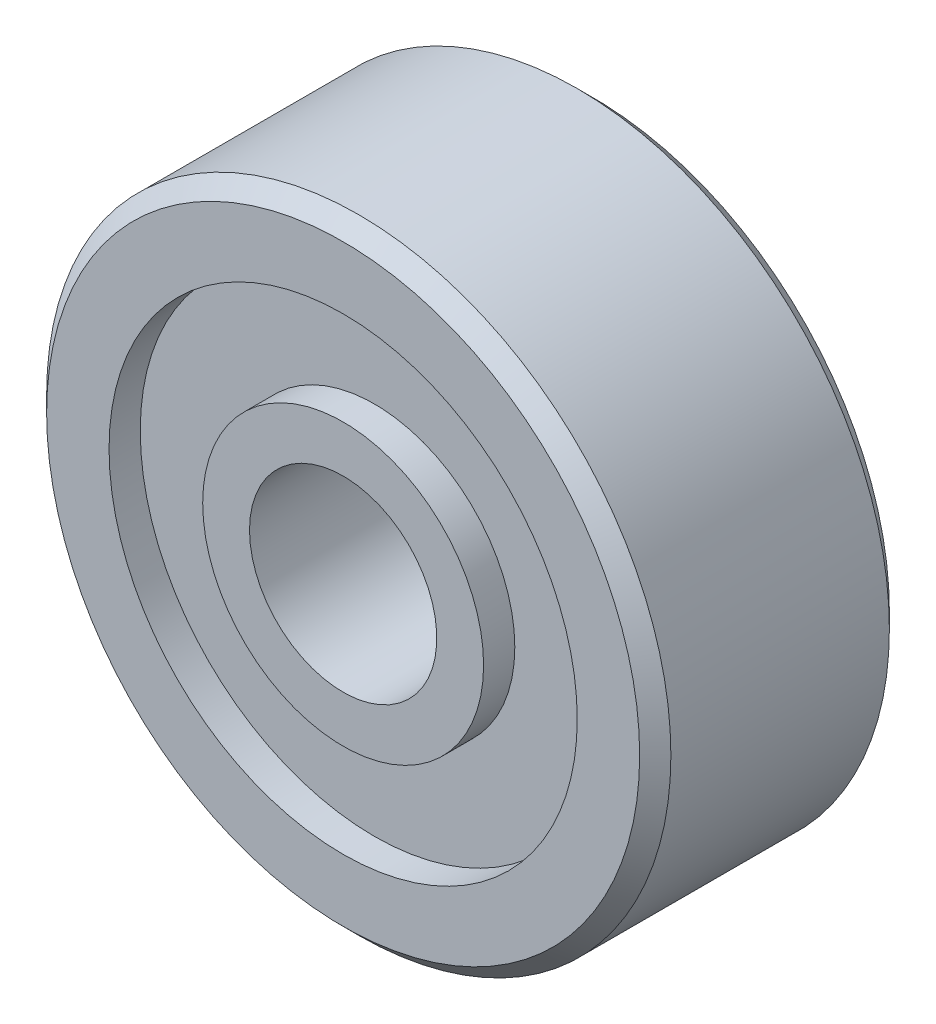
SolidWorks part; units mm, degrees
ref_plane "Front Plane" through (0, 0, 0) normal (0, 0, 1) x (1, 0, 0)
ref_plane "Top Plane" through (0, 0, 0) normal (0, 1, 0) x (1, 0, 0)
ref_plane "Right Plane" through (0, 0, 0) normal (1, 0, 0) x (0, 0, -1)
ref_plane "Plane1" through (0, 0, 0) normal (0, -1, 0) x (1, 0, 0)
sketch "Sketch1" plane through (0, 0, 0) normal (0, -1, 0) x (1, 0, 0)
  line L0 (6.5, 1.25) -> (6.25, 1.5)
  line L1 (6.25, 1.5) -> (5.25, 1.5)
  line L2 (5.25, 1.5) -> (5.25, 1)
  line L3 (5.25, 1) -> (3.75, 1)
  line L4 (3.75, 1) -> (3.75, 1.5)
  line L5 (3.75, 1.5) -> (3, 1.5)
  line L6 (3, 1.5) -> (3, -2.5)
  line L7 (3, -2.5) -> (3.75, -2.5)
  line L8 (3.75, -2.5) -> (3.75, -2)
  line L9 (3.75, -2) -> (5.25, -2)
  line L10 (5.25, -2) -> (5.25, -2.5)
  line L11 (5.25, -2.5) -> (6.25, -2.5)
  line L12 (6.25, -2.5) -> (6.5, -2.25)
  line L13 (6.5, -2.25) -> (6.5, 1.25)
  line L14 (1.5, 2.5) -> (1.5, -2.5) construction
  dimension "D1" = 3
  dimension "D2" = 10
  dimension "D3" = 4.5
  dimension "D4" = 4
  dimension "D5" = 0.5
  dimension "D6" = 45
  dimension "D7" = 0.5
  dimension "D8" = 45
revolve "Revolve1" add sketch "Sketch1" angle 360 about L14 reverse direction yes
